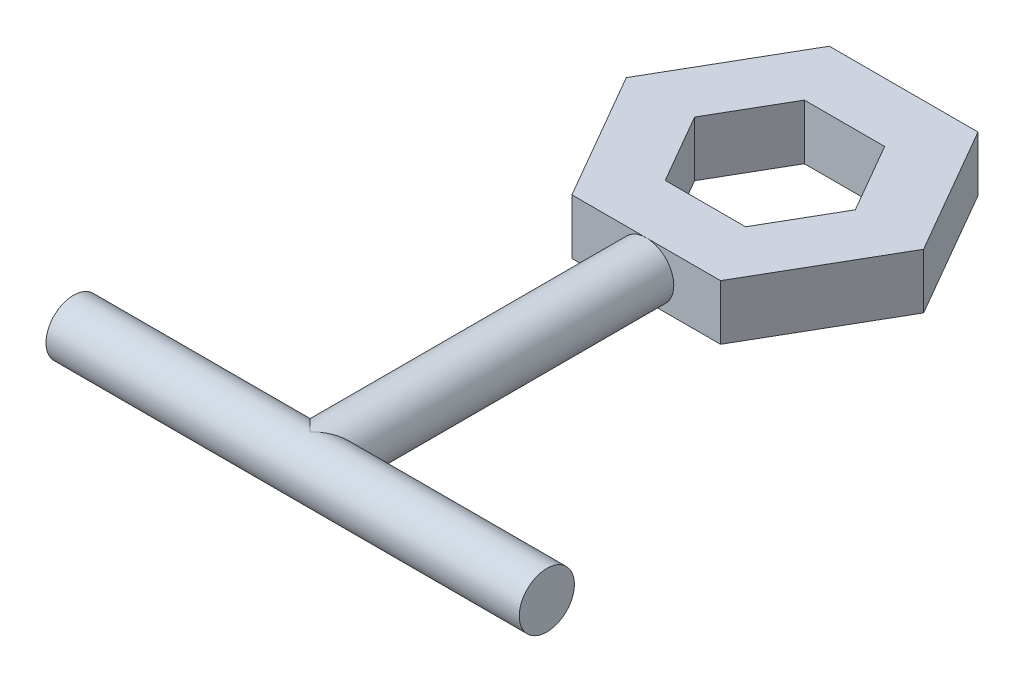
SolidWorks part; units mm, degrees
ref_plane "Front Plane" through (0, 0, 0) normal (0, 0, 1) x (1, 0, 0)
ref_plane "Top Plane" through (0, 0, 0) normal (0, 1, 0) x (1, 0, 0)
ref_plane "Right Plane" through (0, 0, 0) normal (1, 0, 0) x (0, 0, -1)
sketch "Sketch1" plane through (0, 0, 0) normal (0, 1, 0) x (1, 0, 0)
  line L0 (7.9776, 13.8176) -> (-7.9776, 13.8176)
  line L1 (8.6228, 0) -> (4.3114, 7.4676)
  line L2 (4.3114, 7.4676) -> (-4.3114, 7.4676)
  line L3 (-4.3114, 7.4676) -> (-8.6228, 0)
  line L4 (-8.6228, 0) -> (-4.3114, -7.4676)
  line L5 (-4.3114, -7.4676) -> (4.3114, -7.4676)
  line L6 (4.3114, -7.4676) -> (8.6228, 0)
  line L7 (-7.9776, 13.8176) -> (-15.9552, 0)
  line L8 (-15.9552, 0) -> (-7.9776, -13.8176)
  line L9 (-7.9776, -13.8176) -> (7.9776, -13.8176)
  line L10 (7.9776, -13.8176) -> (15.9552, 0)
  line L11 (15.9552, 0) -> (7.9776, 13.8176)
  circle A0 centre (0, 0) radius 7.4676 construction
  dimension "D1" = 14.9352
  dimension "D2" = 6.35
extrude "Boss-Extrude1" add sketch "Sketch1" along normal mid plane 5.9182
sketch "Sketch6" plane through (0, 0, 0) normal (0, 1, 0) x (1, 0, 0)
  line L0 (0, -13.8176) -> (0, -49.8856)
  line L1 (-7.9776, -13.8176) -> (7.9776, -13.8176) construction
  line L2 (25.4, -49.8856) -> (-25.4, -49.8856)
  point P3 (0, -49.8856)
  dimension "D1" = 36.068
  dimension "D2" = 50.8
sweep "Sweep1" add path "Sketch6" circular profile diameter 5.9182 parameters "D3"=5.9182
sweep "Sweep2" add path "Sketch6<4>" circular profile diameter 5.9182 parameters "D3"=5.9182
sketch "Sketch6<4>" plane through (0, 0, 0) normal (0, 1, 0) x (1, 0, 0) same geometry as "Sketch6"
